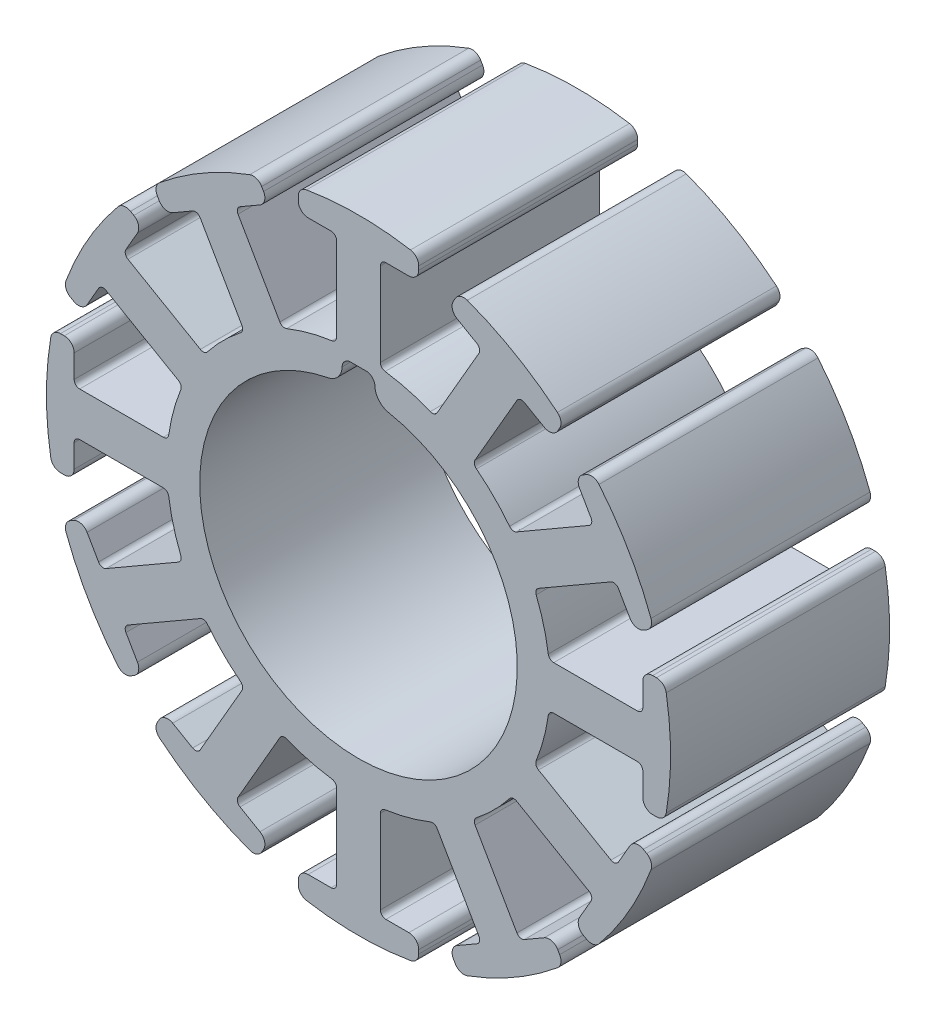
SolidWorks part; units mm, degrees
material "AISI 347 軟ｽﾃﾝﾚｽ鋼 (SS)"
ref_plane "正面" through (0, 0, 0) normal (0, 0, 1) x (1, 0, 0)
ref_plane "平面" through (0, 0, 0) normal (0, 1, 0) x (1, 0, 0)
ref_plane "右側面" through (0, 0, 0) normal (1, 0, 0) x (0, 0, -1)
sketch "ｽｹｯﾁ1" plane through (0, 0, 0) normal (0, 0, 1) x (1, 0, 0)
  line L0 (0, 28.5) -> (0, 0) construction
  line L1 (-5.5, 27.9643) -> (5.5, 27.9643) construction
  line L2 (-2, 25.9643) -> (-2, 17.3853)
  line L3 (2, 25.9643) -> (2, 17.3853)
  line L4 (14.7142, 21.4857) -> (10.4247, 14.0561)
  line L5 (17.7453, 19.7357) -> (14.7142, 21.4857)
  line L6 (-5.5, 27.9643) -> (-5.5, 25.9643)
  line L7 (-5.5, 25.9643) -> (-2, 25.9643)
  line L8 (5.5, 27.9643) -> (5.5, 25.9643)
  line L9 (5.5, 25.9643) -> (2, 25.9643)
  line L10 (18.7453, 21.4678) -> (17.7453, 19.7357)
  line L11 (9.219, 26.9678) -> (8.219, 25.2357)
  line L12 (8.219, 25.2357) -> (11.2501, 23.4857)
  line L13 (11.2501, 23.4857) -> (6.9606, 16.0561)
  line L14 (23.4857, 11.2501) -> (16.0561, 6.9606)
  line L15 (25.2357, 8.219) -> (23.4857, 11.2501)
  line L16 (26.9678, 9.219) -> (25.2357, 8.219)
  line L17 (21.4678, 18.7453) -> (19.7357, 17.7453)
  line L18 (19.7357, 17.7453) -> (21.4857, 14.7142)
  line L19 (21.4857, 14.7142) -> (14.0561, 10.4247)
  line L20 (25.9643, -2) -> (17.3853, -2)
  line L21 (25.9643, -5.5) -> (25.9643, -2)
  line L22 (27.9643, -5.5) -> (25.9643, -5.5)
  line L23 (27.9643, 5.5) -> (25.9643, 5.5)
  line L24 (25.9643, 5.5) -> (25.9643, 2)
  line L25 (25.9643, 2) -> (17.3853, 2)
  line L26 (21.4857, -14.7142) -> (14.0561, -10.4247)
  line L27 (19.7357, -17.7453) -> (21.4857, -14.7142)
  line L28 (21.4678, -18.7453) -> (19.7357, -17.7453)
  line L29 (26.9678, -9.219) -> (25.2357, -8.219)
  line L30 (25.2357, -8.219) -> (23.4857, -11.2501)
  line L31 (23.4857, -11.2501) -> (16.0561, -6.9606)
  line L32 (11.2501, -23.4857) -> (6.9606, -16.0561)
  line L33 (8.219, -25.2357) -> (11.2501, -23.4857)
  line L34 (9.219, -26.9678) -> (8.219, -25.2357)
  line L35 (18.7453, -21.4678) -> (17.7453, -19.7357)
  line L36 (17.7453, -19.7357) -> (14.7142, -21.4857)
  line L37 (14.7142, -21.4857) -> (10.4247, -14.0561)
  line L38 (-2, -25.9643) -> (-2, -17.3853)
  line L39 (-5.5, -25.9643) -> (-2, -25.9643)
  line L40 (-5.5, -27.9643) -> (-5.5, -25.9643)
  line L41 (5.5, -27.9643) -> (5.5, -25.9643)
  line L42 (5.5, -25.9643) -> (2, -25.9643)
  line L43 (2, -25.9643) -> (2, -17.3853)
  line L44 (-14.7142, -21.4857) -> (-10.4247, -14.0561)
  line L45 (-17.7453, -19.7357) -> (-14.7142, -21.4857)
  line L46 (-18.7453, -21.4678) -> (-17.7453, -19.7357)
  line L47 (-9.219, -26.9678) -> (-8.219, -25.2357)
  line L48 (-8.219, -25.2357) -> (-11.2501, -23.4857)
  line L49 (-11.2501, -23.4857) -> (-6.9606, -16.0561)
  line L50 (-23.4857, -11.2501) -> (-16.0561, -6.9606)
  line L51 (-25.2357, -8.219) -> (-23.4857, -11.2501)
  line L52 (-26.9678, -9.219) -> (-25.2357, -8.219)
  line L53 (-21.4678, -18.7453) -> (-19.7357, -17.7453)
  line L54 (-19.7357, -17.7453) -> (-21.4857, -14.7142)
  line L55 (-21.4857, -14.7142) -> (-14.0561, -10.4247)
  line L56 (-25.9643, 2) -> (-17.3853, 2)
  line L57 (-25.9643, 5.5) -> (-25.9643, 2)
  line L58 (-27.9643, 5.5) -> (-25.9643, 5.5)
  line L59 (-27.9643, -5.5) -> (-25.9643, -5.5)
  line L60 (-25.9643, -5.5) -> (-25.9643, -2)
  line L61 (-25.9643, -2) -> (-17.3853, -2)
  line L62 (-21.4857, 14.7142) -> (-14.0561, 10.4247)
  line L63 (-19.7357, 17.7453) -> (-21.4857, 14.7142)
  line L64 (-21.4678, 18.7453) -> (-19.7357, 17.7453)
  line L65 (-26.9678, 9.219) -> (-25.2357, 8.219)
  line L66 (-25.2357, 8.219) -> (-23.4857, 11.2501)
  line L67 (-23.4857, 11.2501) -> (-16.0561, 6.9606)
  line L68 (-11.2501, 23.4857) -> (-6.9606, 16.0561)
  line L69 (-8.219, 25.2357) -> (-11.2501, 23.4857)
  line L70 (-9.219, 26.9678) -> (-8.219, 25.2357)
  line L71 (-18.7453, 21.4678) -> (-17.7453, 19.7357)
  line L72 (-17.7453, 19.7357) -> (-14.7142, 21.4857)
  line L73 (-14.7142, 21.4857) -> (-10.4247, 14.0561)
  circle A0 centre (0, 0) radius 28.5 construction
  arc A1 (-2, 17.3853) -> (-6.9606, 16.0561) centre (0, 0) ccw
  circle A2 centre (0, 0) radius 14.5
  arc A3 (-5.5, 27.9643) -> (5.5, 27.9643) centre (0, 0) cw
  arc A4 (9.219, 26.9678) -> (18.7453, 21.4678) centre (0, 0) cw
  arc A5 (21.4678, 18.7453) -> (26.9678, 9.219) centre (0, 0) cw
  arc A6 (27.9643, 5.5) -> (27.9643, -5.5) centre (0, 0) cw
  arc A7 (26.9678, -9.219) -> (21.4678, -18.7453) centre (0, 0) cw
  arc A8 (18.7453, -21.4678) -> (9.219, -26.9678) centre (0, 0) cw
  arc A9 (5.5, -27.9643) -> (-5.5, -27.9643) centre (0, 0) cw
  arc A10 (-9.219, -26.9678) -> (-18.7453, -21.4678) centre (0, 0) cw
  arc A11 (-21.4678, -18.7453) -> (-26.9678, -9.219) centre (0, 0) cw
  arc A12 (-27.9643, -5.5) -> (-27.9643, 5.5) centre (0, 0) cw
  arc A13 (-26.9678, 9.219) -> (-21.4678, 18.7453) centre (0, 0) cw
  arc A14 (-18.7453, 21.4678) -> (-9.219, 26.9678) centre (0, 0) cw
  arc A15 (6.9606, 16.0561) -> (2, 17.3853) centre (0, 0) ccw
  arc A16 (14.0561, 10.4247) -> (10.4247, 14.0561) centre (0, 0) ccw
  arc A17 (17.3853, 2) -> (16.0561, 6.9606) centre (0, 0) ccw
  arc A18 (16.0561, -6.9606) -> (17.3853, -2) centre (0, 0) ccw
  arc A19 (10.4247, -14.0561) -> (14.0561, -10.4247) centre (0, 0) ccw
  arc A20 (2, -17.3853) -> (6.9606, -16.0561) centre (0, 0) ccw
  arc A21 (-6.9606, -16.0561) -> (-2, -17.3853) centre (0, 0) ccw
  arc A22 (-14.0561, -10.4247) -> (-10.4247, -14.0561) centre (0, 0) ccw
  arc A23 (-17.3853, -2) -> (-16.0561, -6.9606) centre (0, 0) ccw
  arc A24 (-16.0561, 6.9606) -> (-17.3853, 2) centre (0, 0) ccw
  arc A25 (-10.4247, 14.0561) -> (-14.0561, 10.4247) centre (0, 0) ccw
  point P105 (0, 0)
  dimension "D1" = 57
  dimension "D4" = 29
  dimension "D5" = 35
  dimension "D2" = 2
  dimension "D3" = 2
  dimension "D6" = 11
  dimension "D7" = 2
  dimension "D8" = 12
extrude "ﾎﾞｽ - 押し出し1" add sketch "ｽｹｯﾁ1" along normal blind 20
fillet "ﾌｨﾚｯﾄ1" radius 0.9 4 edges at (-17.7453, 19.7357, 10) (-18.7453, 21.4678, 10) (-9.219, 26.9678, 10) (-8.219, 25.2357, 10)
fillet "ﾌｨﾚｯﾄ2" radius 0.9 12 edges at (25.2357, 8.219, 10) (17.7453, 19.7357, 10) (19.7357, 17.7453, 10) (26.9678, 9.219, 10) (5.5, 25.9643, 10) (21.4678, 18.7453, 10) (18.7453, 21.4678, 10) (8.219, 25.2357, 10) (9.219, 26.9678, 10) (5.5, 27.9643, 10) (-5.5, 25.9643, 10) (-5.5, 27.9643, 10)
fillet "ﾌｨﾚｯﾄ3" radius 0.9 8 edges at (21.4678, -18.7453, 10) (19.7357, -17.7453, 10) (26.9678, -9.219, 10) (25.2357, -8.219, 10) (25.9643, 5.5, 10) (25.9643, -5.5, 10) (27.9643, -5.5, 10) (27.9643, 5.5, 10)
fillet "ﾌｨﾚｯﾄ4" radius 0.9 24 edges at (-21.4678, 18.7453, 10) (-19.7357, 17.7453, 10) (-26.9678, 9.219, 10) (-25.2357, 8.219, 10) (-25.9643, 5.5, 10) (-27.9643, 5.5, 10) (-25.9643, -5.5, 10) (-27.9643, -5.5, 10) (-25.2357, -8.219, 10) (-26.9678, -9.219, 10) (-21.4678, -18.7453, 10) (-19.7357, -17.7453, 10) (-17.7453, -19.7357, 10) (-18.7453, -21.4678, 10) (-9.219, -26.9678, 10) (-8.219, -25.2357, 10) (-5.5, -25.9643, 10) (-5.5, -27.9643, 10) (5.5, -25.9643, 10) (5.5, -27.9643, 10) (9.219, -26.9678, 10) (8.219, -25.2357, 10) (18.7453, -21.4678, 10) (17.7453, -19.7357, 10)
fillet "ﾌｨﾚｯﾄ5" radius 0.5 26 edges at (-23.4857, -11.2501, 10) (-16.0561, -6.9606, 10) (-21.4857, -14.7142, 10) (-14.0561, -10.4247, 10) (-14.7142, -21.4857, 10) (-10.4247, -14.0561, 10) (-11.2501, -23.4857, 10) (-6.9606, -16.0561, 10) (-2, -25.9643, 10) (-2, -17.3853, 10) (2, -25.9643, 10) (2, -17.3853, 10) (6.9606, -16.0561, 10) (11.2501, -23.4857, 10) (14.7142, -21.4857, 10) (10.4247, -14.0561, 10) (21.4857, -14.7142, 10) (14.0561, -10.4247, 10) (23.4857, -11.2501, 10) (16.0561, -6.9606, 10) (17.3853, -2, 10) (25.9643, -2, 10) (25.9643, 2, 10) (17.3853, 2, 10) (16.0561, 6.9606, 10) (23.4857, 11.2501, 10)
fillet "ﾌｨﾚｯﾄ6" radius 0.5 22 edges at (21.4857, 14.7142, 10) (14.0561, 10.4247, 10) (10.4247, 14.0561, 10) (14.7142, 21.4857, 10) (11.2501, 23.4857, 10) (6.9606, 16.0561, 10) (-2, 17.3853, 10) (-2, 25.9643, 10) (2, 25.9643, 10) (-11.2501, 23.4857, 10) (-10.4247, 14.0561, 10) (-21.4857, 14.7142, 10) (-14.7142, 21.4857, 10) (-23.4857, 11.2501, 10) (-16.0561, 6.9606, 10) (2, 17.3853, 10) (-6.9606, 16.0561, 10) (-14.0561, 10.4247, 10) (-25.9643, 2, 10) (-17.3853, 2, 10) (-25.9643, -2, 10) (-17.3853, -2, 10)
sketch "ｽｹｯﾁ3" plane through (0, 0, 20) normal (0, 0, 1) x (1, 0, 0)
  line L1 (-1.5, 12.5) -> (1.5, 12.5)
  line L2 (-1.5, 12.5) -> (-1.5, 16.5)
  line L3 (-1.5, 16.5) -> (1.5, 16.5)
  line L4 (1.5, 12.5) -> (1.5, 16.5)
  line L5 (-1.5, 12.5) -> (1.5, 16.5) construction
  line L6 (-1.5, 16.5) -> (1.5, 12.5) construction
  circle A0 centre (0, 0) radius 14.5 construction
  point P0 (0, 14.5)
  dimension "D1" = 3
  dimension "D2" = 2
extrude "ｶｯﾄ - 押し出し1" cut sketch "ｽｹｯﾁ3" against normal through all
fillet "ﾌｨﾚｯﾄ7" radius 1.55 2 edges at (1.5, 14.4222, 10) (-1.5, 14.4222, 10)
fillet "ﾌｨﾚｯﾄ8" radius 0.8 2 edges at (1.5, 16.5, 10) (-1.5, 16.5, 10)
